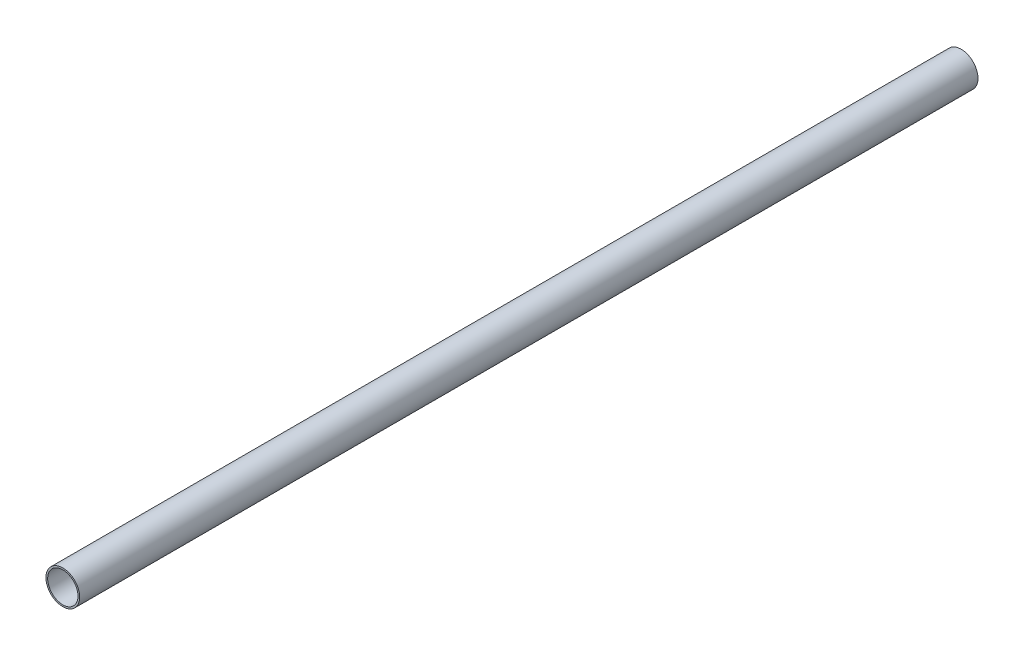
SolidWorks part; units mm, degrees
ref_plane "Front Plane" through (0, 0, 0) normal (0, 0, 1) x (1, 0, 0)
ref_plane "Top Plane" through (0, 0, 0) normal (0, 1, 0) x (1, 0, 0)
ref_plane "Right Plane" through (0, 0, 0) normal (1, 0, 0) x (0, 0, -1)
sketch "Sketch1" plane through (0, 0, 0) normal (0, 0, 1) x (1, 0, 0)
  circle A0 centre (0, 0) radius 15
  dimension "D1" = 30
extrude "Boss-Extrude1" add sketch "Sketch1" along normal blind 800
sketch "Sketch2" plane through (0, 0, 0) normal (0, 0, -1) x (-1, 0, 0)
  circle A0 centre (0, 0) radius 13.5
  dimension "D1" = 27
extrude "Cut-Extrude1" cut sketch "Sketch2" against normal through all
